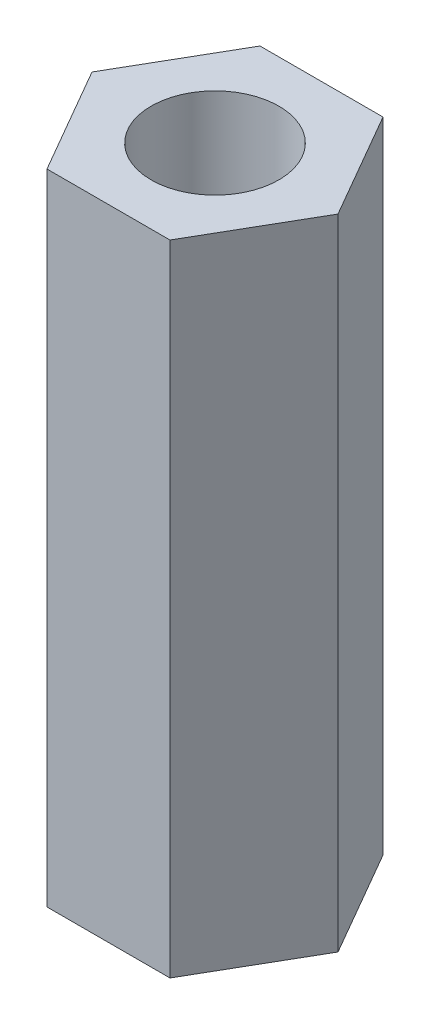
SolidWorks part; units mm, degrees
material "ABS"
ref_plane "Alzado" through (0, 0, 0) normal (0, 0, 1) x (1, 0, 0)
ref_plane "Planta" through (0, 0, 0) normal (0, 1, 0) x (1, 0, 0)
ref_plane "Vista lateral" through (0, 0, 0) normal (1, 0, 0) x (0, 0, -1)
sketch "Croquis1" plane through (0, 0, 0) normal (0, 1, 0) x (1, 0, 0)
  line L1 (1.4434, -2.5) -> (2.8868, 0)
  line L2 (2.8868, 0) -> (1.4434, 2.5)
  line L3 (1.4434, 2.5) -> (-1.4434, 2.5)
  line L4 (-1.4434, 2.5) -> (-2.8868, 0)
  line L5 (-2.8868, 0) -> (-1.4434, -2.5)
  line L6 (-1.4434, -2.5) -> (1.4434, -2.5)
  circle A0 centre (0, 0) radius 2.5 construction
  circle A1 centre (0, 0) radius 1.5
  dimension "D2" = 3
  dimension "D1" = 5
extrude "Saliente-Extruir1" add sketch "Croquis1" along normal mid plane 12
sketch "草图1" plane through (0, 6, 0) normal (0, 1, 0) x (1, 0, 0)
  line L6 (-1.4434, -2.5) -> (1.4434, -2.5)
  line L7 (1.4434, -2.5) -> (2.8868, 0)
  line L8 (2.8868, 0) -> (1.4434, 2.5)
  line L9 (1.4434, 2.5) -> (-1.4434, 2.5)
  line L10 (-1.4434, 2.5) -> (-2.8868, 0)
  line L11 (-2.8868, 0) -> (-1.4434, -2.5)
  line L12 (-1.4434, -2.5) -> (1.4434, -2.5)
  line L13 (1.4434, -2.5) -> (2.8868, 0)
  line L14 (2.8868, 0) -> (1.4434, 2.5)
  line L15 (1.4434, 2.5) -> (-1.4434, 2.5)
  line L16 (-1.4434, 2.5) -> (-2.8868, 0)
  line L17 (-2.8868, 0) -> (-1.4434, -2.5)
  circle A0 centre (0, 0) radius 1.5 construction
  circle A1 centre (0, 0) radius 1.5
  dimension "D1" = 0
extrude "凸台-拉伸1" add sketch "草图1" along normal blind 3
